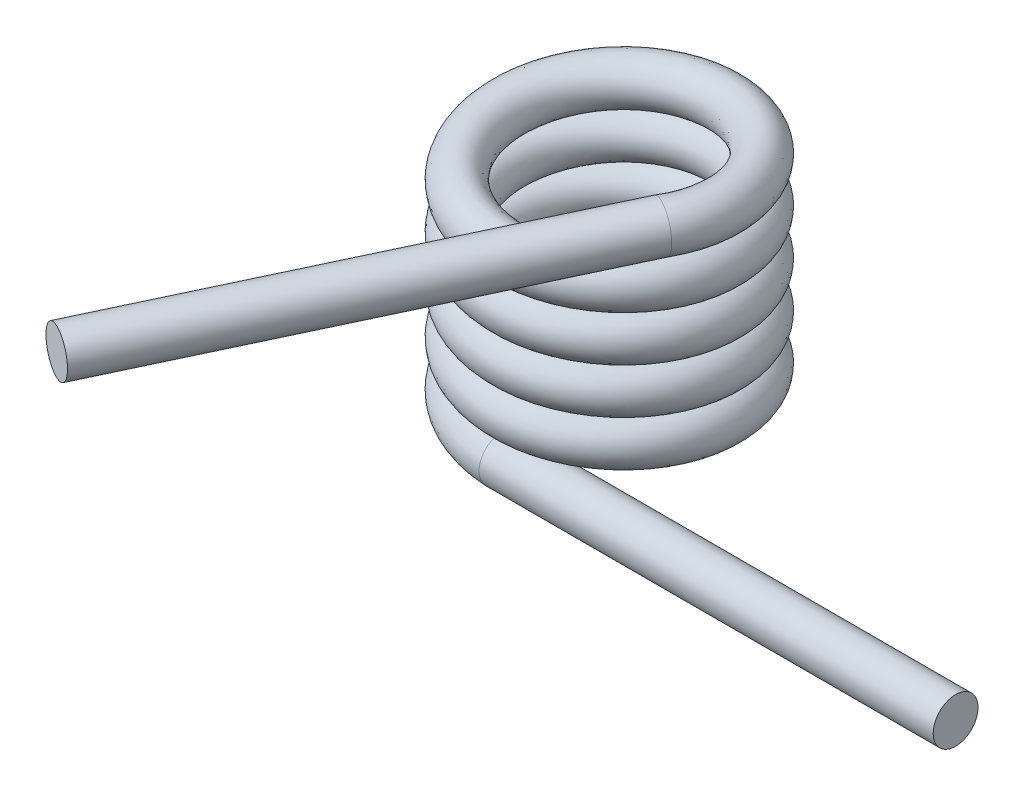
SolidWorks part; units mm, degrees
material "AISI 1020"
ref_plane "Спереди" through (0, 0, 0) normal (0, 0, 1) x (1, 0, 0)
ref_plane "Сверху" through (0, 0, 0) normal (0, 1, 0) x (1, 0, 0)
ref_plane "Справа" through (0, 0, 0) normal (1, 0, 0) x (0, 0, -1)
sketch "Эскиз1" plane through (0, 0, 0) normal (0, 1, 0) x (1, 0, 0)
  circle A0 centre (0, 0) radius 23 construction
  circle A1 centre (0, 0) radius 15 construction
  circle A2 centre (0, 0) radius 19
  dimension "D1" = 46
  dimension "D2" = 30
  dimension "D3" = 38
curve "Спираль1" pitch 8 height 38.56 radius 19 left hand yes centre (0, 0, 0) axis (0, 1, 0) start towards (0, 0, 1)
ref_plane "Плоскость1" through (0, 0, 0) normal (-1, 0, 0) x (0, 0, 1)
sketch "Эскиз2" plane through (0, 0, 0) normal (-1, 0, 0) x (0, 0, 1)
  circle A0 centre (19, 0) radius 3.95
  dimension "D1" = 7.9
sweep "По траектории1" add profiles "Эскиз2" path "Спираль1"
extrude "Бобышка-Вытянуть1" add sketch "Эскиз2<2>" against normal blind 80
sketch "Эскиз2<2>" plane through (0, 0, 0) normal (-1, 0, 0) x (0, 0, 1) same geometry as "Эскиз2"
sketch "Эскиз4" plane through (0, 0, 0) normal (-0.4258, 0, 0.9048) x (0.9048, 0, 0.4258)
  circle A0 centre (19, 38.5599) radius 3.95 construction
  circle A1 centre (19, 38.5599) radius 3.95
extrude "Бобышка-Вытянуть2" add sketch "Эскиз4" along normal blind 80
sketch "Эскиз5" plane through (0, 0, 0) normal (0, 1, 0) x (1, 0, 0)
  line L0 (0, -19) -> (80, -19)
  line L1 (0, 10.45) -> (0, -10.45) construction
  line L2 (17.1546, -8.1683) -> (-17.2383, -80.398)
  line L3 (80, -22.95) -> (80, -15.05) construction
  circle A0 centre (0, 0) radius 19
  dimension "D1" = 115
ref_axis "Ось1" through (-10.6817, 38.5599, 67.3238) along (0.4258, 0, -0.9048)
equation "\"D3@Эскиз1\"=(\"D2@Эскиз1\"+\"D1@Эскиз1\")/2"
